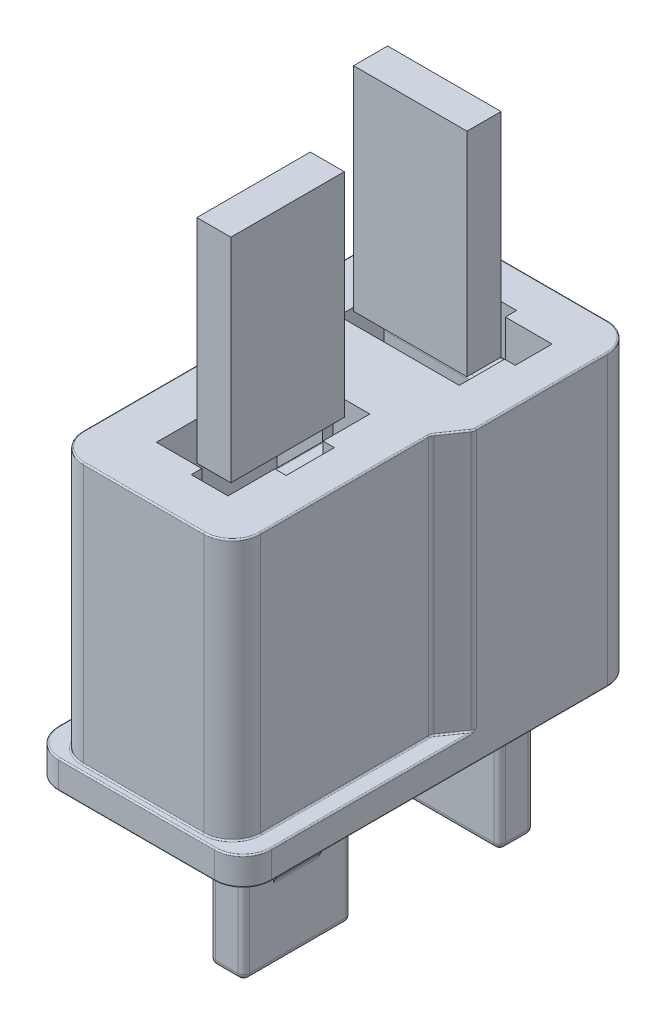
SolidWorks part; units mm, degrees
ref_plane "Front Plane" through (0, 0, 0) normal (0, 0, 1) x (1, 0, 0)
ref_plane "Top Plane" through (0, 0, 0) normal (0, 1, 0) x (1, 0, 0)
ref_plane "Right Plane" through (0, 0, 0) normal (1, 0, 0) x (0, 0, -1)
sketch "Sketch1" plane through (0, 0, 0) normal (0, 1, 0) x (1, 0, 0)
  line L1 (-3.75, -6.8) -> (3.75, -6.8)
  line L2 (-3.75, -6.8) -> (-3.75, 6.8)
  line L3 (-3.75, 6.8) -> (3.75, 6.8)
  line L4 (3.75, -6.8) -> (3.75, 6.8)
  line L5 (-3.75, -6.8) -> (3.75, 6.8) construction
  line L6 (-3.75, 6.8) -> (3.75, -6.8) construction
  point P0 (0, 0)
  dimension "D1" = 7.5
  dimension "D2" = 13.6
extrude "Boss-Extrude1" add sketch "Sketch1" along normal blind 7 and the other way blind 3.2
sketch "Sketch2" plane through (0, 7, 0) normal (0, 1, 0) x (1, 0, 0)
  line L0 (0, 0) -> (0, -6.8) construction
  line L1 (-3.75, -6.8) -> (3.75, -6.8) construction
  line L2 (3.125, -6.8) -> (3.125, 0.2)
  line L3 (3.125, 0.2) -> (3.75, 1.1)
  line L4 (3.75, -6.8) -> (3.75, 6.8) construction
  line L5 (3.75, 1.1) -> (3.75, -6.8)
  line L6 (3.75, -6.8) -> (3.125, -6.8)
  line L7 (-3.75, -6.8) -> (-3.125, -6.8)
  line L8 (-3.75, 1.1) -> (-3.75, -6.8)
  line L9 (-3.125, -6.8) -> (-3.125, 0.2)
  line L10 (-3.125, 0.2) -> (-3.75, 1.1)
  line L11 (3.75, 6.8) -> (-3.75, 6.8) construction
  dimension "D1" = 6.25
  dimension "D2" = 5.7
  dimension "D3" = 7
extrude "Cut-Extrude1" cut sketch "Sketch2" against normal through all
fillet "Fillet1" radius 1 4 edges at (-3.75, 1.9, -6.8) (3.75, 1.9, -6.8) (3.125, 1.9, 6.8) (-3.125, 1.9, 6.8)
fillet "Fillet2" radius 0.25 4 edges at (-3.125, 1.9, -0.2) (-3.75, 1.9, -1.1) (3.125, 1.9, -0.2) (3.75, 1.9, -1.1)
sketch "Sketch12" plane through (0, 7, 0) normal (0, 1, 0) x (1, 0, 0)
  line L0 (0, 0) -> (0, 4.45) construction
  line L1 (0, 0) -> (0, -2.75) construction
  line L2 (0, -2.75) -> (0.775, -2.75) construction
  line L3 (2.75, 6.8) -> (-2.75, 6.8) construction
  line L4 (-2.5, 5.1) -> (2.5, 5.1)
  line L5 (-2.5, 5.1) -> (-2.5, 3.8)
  line L6 (-2.5, 3.8) -> (2.5, 3.8)
  line L7 (2.5, 5.1) -> (2.5, 3.8)
  line L8 (-2.5, 5.1) -> (2.5, 3.8) construction
  line L9 (-2.5, 3.8) -> (2.5, 5.1) construction
  line L10 (0.125, -0.25) -> (1.425, -0.25)
  line L11 (0.125, -0.25) -> (0.125, -5.25)
  line L12 (0.125, -5.25) -> (1.425, -5.25)
  line L13 (1.425, -0.25) -> (1.425, -5.25)
  line L14 (0.125, -0.25) -> (1.425, -5.25) construction
  line L15 (0.125, -5.25) -> (1.425, -0.25) construction
  line L16 (3.125, 0.1217) -> (3.125, -5.8) construction
  line L17 (-2.125, -6.8) -> (2.125, -6.8) construction
  dimension "D1" = 5
  dimension "D2" = 1.3
  dimension "D3" = 1.7
  dimension "D4" = 1.7
  dimension "D5" = 1.55
extrude "Cut-Extrude4" cut sketch "Sketch12" against normal blind 8
sketch "Sketch13" plane through (0, 7, 0) normal (0, 1, 0) x (1, 0, 0)
  line L0 (0, 3.8) -> (0, 3) construction
  line L1 (-2.5, 3.8) -> (2.5, 3.8) construction
  line L2 (0.125, -2.75) -> (-0.675, -2.75) construction
  line L3 (0.125, -0.25) -> (0.125, -5.25) construction
  line L4 (-3.125, -5.8) -> (-3.125, 0.1217) construction
  line L5 (-2.125, 2.2) -> (2.125, 2.2)
  line L6 (-2.125, 2.2) -> (-2.125, 3.8)
  line L7 (-2.125, 3.8) -> (2.125, 3.8)
  line L8 (2.125, 2.2) -> (2.125, 3.8)
  line L9 (-2.125, 2.2) -> (2.125, 3.8) construction
  line L10 (-2.125, 3.8) -> (2.125, 2.2) construction
  line L11 (-1.475, -4.875) -> (0.125, -4.875)
  line L12 (-1.475, -4.875) -> (-1.475, -0.625)
  line L13 (-1.475, -0.625) -> (0.125, -0.625)
  line L14 (0.125, -4.875) -> (0.125, -0.625)
  line L15 (-1.475, -4.875) -> (0.125, -0.625) construction
  line L16 (-1.475, -0.625) -> (0.125, -4.875) construction
  dimension "D1" = 4.25
  dimension "D2" = 1.65
extrude "Cut-Extrude5" cut sketch "Sketch13" against normal up to surface (8 mm away) up to face at (0, -1, -4.45)
sketch "Sketch14" plane through (0, -3.2, 0) normal (0, -1, 0) x (1, 0, 0)
  line L0 (-3.75, -3.4891) -> (-3.75, 7.05)
  line L1 (-3.75, -5.8) -> (-3.75, -1.1783) construction
  line L2 (-3.75, 7.05) -> (3.75, 7.05)
  line L3 (3.75, 7.05) -> (3.75, -3.4891)
  line L4 (3.75, -1.1783) -> (3.75, -5.8) construction
  line L5 (3.75, -3.4891) -> (-3.75, -3.4891)
  line L6 (-2.125, 6.8) -> (2.125, 6.8) construction
  dimension "D1" = 0.25
extrude "Boss-Extrude5" add sketch "Sketch14" against normal blind 1
fillet "Fillet8" radius 1 2 edges at (3.75, -2.7, 7.05) (-3.75, -2.7, 7.05)
sketch "Sketch15" plane through (0, 7, 0) normal (0, 1, 0) x (1, 0, 0)
  line L0 (0, 5.1) -> (0, 5.3) construction
  line L1 (2.5, 5.1) -> (-2.5, 5.1) construction
  line L2 (1.425, -2.75) -> (1.625, -2.75) construction
  line L3 (1.425, -5.25) -> (1.425, -0.25) construction
  line L5 (-0.85, 5.5) -> (0.85, 5.5)
  line L6 (-0.85, 5.5) -> (-0.85, 5.1)
  line L7 (-0.85, 5.1) -> (0.85, 5.1)
  line L8 (0.85, 5.5) -> (0.85, 5.1)
  line L9 (-0.85, 5.5) -> (0.85, 5.1) construction
  line L10 (-0.85, 5.1) -> (0.85, 5.5) construction
  line L11 (1.825, -1.9) -> (1.425, -1.9)
  line L12 (1.825, -1.9) -> (1.825, -3.6)
  line L13 (1.825, -3.6) -> (1.425, -3.6)
  line L14 (1.425, -1.9) -> (1.425, -3.6)
  line L15 (1.825, -1.9) -> (1.425, -3.6) construction
  line L16 (1.825, -3.6) -> (1.425, -1.9) construction
  dimension "D1" = 1.7
  dimension "D2" = 0.4
extrude "Cut-Extrude6" cut sketch "Sketch15" against normal up to surface (8 mm away) up to face at (0, -1, -3.725)
sketch "Sketch16" plane through (0, -1, 0) normal (0, 1, 0) x (1, 0, 0)
  line L0 (-2.45, 5.05) -> (-2.45, 3.85)
  line L1 (-2.5, 5.1) -> (2.5, 5.1) construction
  line L2 (-2.5, 5.1) -> (-2.5, 3.8) construction
  line L3 (-2.5, 3.8) -> (2.5, 3.8) construction
  line L4 (2.5, 5.1) -> (2.5, 3.8) construction
  line L5 (-2.45, 3.85) -> (2.45, 3.85)
  line L6 (2.45, 5.05) -> (2.45, 3.85)
  line L7 (-2.45, 5.05) -> (2.45, 5.05)
  line L8 (1.375, -0.3) -> (1.375, -5.2)
  line L9 (1.425, -0.25) -> (0.125, -0.25) construction
  line L10 (1.425, -0.25) -> (1.425, -5.25) construction
  line L11 (1.425, -5.25) -> (0.125, -5.25) construction
  line L12 (0.125, -0.25) -> (0.125, -5.25) construction
  line L13 (1.375, -5.2) -> (0.175, -5.2)
  line L14 (0.175, -0.3) -> (0.175, -5.2)
  line L15 (1.375, -0.3) -> (0.175, -0.3)
  dimension "D1" = 0.05
  dimension "D2" = 0.05
extrude "Boss-Extrude6" add sketch "Sketch16" along normal blind 6.8
fillet "Fillet9" radius 0.1 16 edges at (1.375, 5.8, 2.75) (0.775, 5.8, 5.2) (0.175, 5.8, 2.75) (0.775, 5.8, 0.3) (2.45, 5.8, -4.45) (0, 5.8, -3.85) (-2.45, 5.8, -4.45) (0, 5.8, -5.05) (0.175, 2.4, 5.2) (1.375, 2.4, 5.2) (1.375, 2.4, 0.3) (0.175, 2.4, 0.3) (-2.45, 2.4, -5.05) (-2.45, 2.4, -3.85) (2.45, 2.4, -5.05) (2.45, 2.4, -3.85)
sketch "Sketch3" plane through (0, 7, 0) normal (0, 1, 0) x (1, 0, 0)
  line L0 (0, 0) -> (0, 3.2) construction
  line L1 (0, 0) -> (0, -2.8) construction
  line L2 (-2, 2.6) -> (2, 2.6)
  line L3 (-2, 2.6) -> (-2, 3.8)
  line L4 (-2, 3.8) -> (2, 3.8)
  line L5 (2, 2.6) -> (2, 3.8)
  line L6 (-2, 2.6) -> (2, 3.8) construction
  line L7 (-2, 3.8) -> (2, 2.6) construction
  line L8 (0, -2.8) -> (0.475, -2.8) construction
  line L9 (2.75, 6.8) -> (-2.75, 6.8) construction
  line L10 (-0.125, -4.8) -> (1.075, -4.8)
  line L11 (-0.125, -4.8) -> (-0.125, -0.8)
  line L12 (-0.125, -0.8) -> (1.075, -0.8)
  line L13 (1.075, -4.8) -> (1.075, -0.8)
  line L14 (-0.125, -4.8) -> (1.075, -0.8) construction
  line L15 (-0.125, -0.8) -> (1.075, -4.8) construction
  line L16 (-3.125, -5.8) -> (-3.125, 0.1217) construction
  line L17 (-2.125, -6.8) -> (2.125, -6.8) construction
  dimension "D1" = 4
  dimension "D2" = 1.2
  dimension "D3" = 3
  dimension "D4" = 3
  dimension "D5" = 2
extrude "Boss-Extrude2" add sketch "Sketch3" along normal blind 7.5
sketch "Sketch4" plane through (0, -3.2, 0) normal (0, -1, 0) x (1, 0, 0)
  line L0 (1.375, 2.75) -> (0.175, 2.75) construction
  line L2 (-2.35, -3.85) -> (2.35, -3.85) construction
  line L3 (0.175, 4.65) -> (1.375, 4.65)
  line L4 (0.175, 4.65) -> (0.175, 0.85)
  line L5 (0.175, 0.85) -> (1.375, 0.85)
  line L6 (1.375, 4.65) -> (1.375, 0.85)
  line L7 (0.175, 4.65) -> (1.375, 0.85) construction
  line L8 (0.175, 0.85) -> (1.375, 4.65) construction
  line L31 (2.35, -5.05) -> (-2.35, -5.05) construction
  line L32 (-2.35, -3.85) -> (2.35, -3.85) construction
  line L33 (2.35, -5.05) -> (-2.35, -5.05) construction
  line L34 (0.175, 0.4) -> (0.175, 5.1) construction
  line L35 (1.375, 5.1) -> (1.375, 0.4) construction
  line L36 (0.175, 0.4) -> (0.175, 5.1) construction
  line L37 (1.375, 5.1) -> (1.375, 0.4) construction
  line L38 (0, -5.05) -> (0, -3.85) construction
  line L40 (-1.9, -3.85) -> (1.9, -3.85)
  line L41 (-1.9, -3.85) -> (-1.9, -5.05)
  line L42 (-1.9, -5.05) -> (1.9, -5.05)
  line L43 (1.9, -3.85) -> (1.9, -5.05)
  line L44 (-1.9, -3.85) -> (1.9, -5.05) construction
  line L45 (-1.9, -5.05) -> (1.9, -3.85) construction
  point P2 (0.775, 2.75)
  point P32 (0, -4.45)
  dimension "D4" = 3.8
extrude "Boss-Extrude3" add sketch "Sketch4" along normal blind 5
sketch "Sketch5" plane through (0, 0, -3.85) normal (0, 0, 1) x (1, 0, 0)
  line L0 (0, -3.2) -> (0, -5.2) construction
  line L2 (0.8, -3.2) -> (-0.8, -3.2)
  line L3 (-0.8, -3.2) -> (-0.8, -5.2)
  line L4 (-0.8, -5.2) -> (0.8, -5.2)
  line L5 (0.8, -3.2) -> (0.8, -5.2)
  line L6 (1.9, -3.2) -> (-1.9, -3.2) construction
  dimension "D1" = 1.6
  dimension "D2" = 2
extrude "Cut-Extrude2" cut sketch "Sketch5" against normal up to next (1.2 mm away)
sketch "Sketch6" plane through (-0.8, 0, 0) normal (1, 0, 0) x (0, 0, -1)
  line L0 (4.35, -3.2) -> (4.35, -4)
  line L1 (5.05, -3.2) -> (3.85, -3.2) construction
  line L3 (3.85, -3.2) -> (3.85, -5.2) construction
  arc A0 (4.35, -4) -> (3.85, -5.2) centre (2.66, -4) cw
  dimension "D1" = 0.5
  dimension "D2" = 0.8
extrude "Extrude-Thin1" add sketch "Sketch6" along normal up to surface (1.6 mm away) thin up to face at (0.8, -4.2, -4.45) thin type one direction reverse wall 1.2
sketch "Sketch7" plane through (1.375, 0, 0) normal (1, 0, 0) x (0, 0, -1)
  line L0 (3.85, -3.2) -> (3.85, -5.2) construction
  line L1 (-2.8, -3.2) -> (-2.8, -5.2) construction
  line L2 (-2, -5.2) -> (-3.6, -5.2)
  line L3 (-3.6, -5.2) -> (-3.6, -3.2)
  line L4 (-3.6, -3.2) -> (-2, -3.2)
  line L5 (-2, -5.2) -> (-2, -3.2)
  line L7 (-0.85, -3.2) -> (-4.65, -3.2) construction
  dimension "D1" = 1.6
extrude "Cut-Extrude3" cut sketch "Sketch7" against normal through all
sketch "Sketch8" plane through (0, 0, 3.6) normal (0, 0, -1) x (-1, 0, 0)
  line L0 (-0.675, -3.2) -> (-0.675, -4)
  line L1 (-0.175, -3.2) -> (-1.375, -3.2) construction
  line L2 (0.8, -3.2) -> (0.8, -4) construction
  line L3 (-0.175, -3.2) -> (-0.175, -5.2) construction
  line L4 (-0.675, -3.2) -> (-1.075, -3.2) construction
  arc A0 (-0.675, -4) -> (-0.175, -5.2) centre (1.015, -4) ccw
  dimension "D1" = 0.5
extrude "Extrude-Thin2" add sketch "Sketch8" along normal up to surface (1.6 mm away) thin up to face at (0.775, -4.2, 2) thin type one direction wall 1.2
sketch "Sketch9" plane through (0, -3.2, 0) normal (0, -1, 0) x (1, 0, 0)
  line L0 (-1.125, 2.8) -> (0.675, 2.8) construction
  line L1 (0.675, 2) -> (0.675, 3.6) construction
  line L2 (-1.125, 3.8) -> (-1.125, 1.8) construction
  line L3 (-0.975, 3.8) -> (-0.975, 1.8)
  line L4 (-1.275, 3.8) -> (-1.275, 1.8)
  line L5 (0.175, 4.65) -> (0.175, 3.6) construction
  line L6 (0, -4.35) -> (0, -2.35) construction
  line L7 (0.8, -4.35) -> (-0.8, -4.35) construction
  line L8 (1, -2.35) -> (-1, -2.35) construction
  line L10 (1, -2.5) -> (-1, -2.5)
  line L11 (1, -2.2) -> (-1, -2.2)
  line L12 (0, -3.35) -> (0, -1.35) construction
  line L13 (-0.15, -3.35) -> (-0.15, -1.35)
  line L14 (0.15, -3.35) -> (0.15, -1.35)
  line L15 (-0.8, -3.85) -> (-1.9, -3.85) construction
  arc A0 (-0.975, 3.8) -> (-1.275, 3.8) centre (-1.125, 3.8) ccw
  arc A1 (-1.275, 1.8) -> (-0.975, 1.8) centre (-1.125, 1.8) ccw
  arc A2 (1, -2.5) -> (1, -2.2) centre (1, -2.35) ccw
  arc A3 (-1, -2.2) -> (-1, -2.5) centre (-1, -2.35) ccw
  arc A4 (-0.15, -3.35) -> (0.15, -3.35) centre (0, -3.35) ccw
  arc A5 (0.15, -1.35) -> (-0.15, -1.35) centre (0, -1.35) ccw
  point P6 (-1.125, 2.8)
  point P20 (0, -2.35)
  point P29 (0, -2.35)
  dimension "D4" = 0.15
  dimension "D3" = 1.5
  dimension "D1" = 1.3
  dimension "D2" = 2
extrude "Boss-Extrude4" add sketch "Sketch9" along normal blind 0.11 contours L4 A1 L3 A0 | L14 A5 L13 L11 | L10 A2 L11 L14 | L13 A4 L14 L10 | L11 A3 L10 L13 | L10 L14 L11 L13
fillet "Fillet3" radius 0.1 16 edges at (-1.125, -3.31, 3.95) (-0.975, -3.31, 2.8) (-1.125, -3.31, 1.65) (-1.275, -3.31, 2.8) (0.575, -3.31, -2.2) (1.15, -3.31, -2.35) (0.575, -3.31, -2.5) (0.15, -3.31, -2.925) (0, -3.31, -3.5) (-0.15, -3.31, -2.925) (-0.575, -3.31, -2.5) (-1.15, -3.31, -2.35) (-0.575, -3.31, -2.2) (-0.15, -3.31, -1.775) (0, -3.31, -1.2) (0.15, -3.31, -1.775)
fillet "Fillet4" radius 0.2 20 edges at (0, -8.2, -5.05) (-1.9, -8.2, -4.45) (0, -8.2, -3.85) (1.9, -8.2, -4.45) (0.775, -8.2, 0.85) (0.175, -8.2, 2.75) (0.775, -8.2, 4.65) (1.375, -8.2, 2.75) (0, -5.6248, -5.05) (1.375, -5.6248, 2.8) (0.175, -5.2, 2.8) (1.375, -5.7, 4.65) (1.375, -5.7, 0.85) (0.175, -5.7, 0.85) (0.175, -5.7, 4.65) (0, -5.2, -3.85) (1.9, -5.7, -3.85) (1.9, -5.7, -5.05) (-1.9, -5.7, -5.05) (-1.9, -5.7, -3.85)
fillet "Fillet5" [suppressed] radius 0.05
fillet "Fillet6" radius 0.05 40 edges at (-3.4571, 7, -6.5071) (0, 7, -6.8) (3.4571, 7, -6.5071) (3.75, 7, -3.4891) (3.7386, 7, -1.1036) (3.4375, 7, -0.65) (3.1364, 7, -0.1964) (3.125, 7, 2.8391) (2.8321, 7, 6.5071) (0, 7, 6.8) (-2.8321, 7, 6.5071) (-3.125, 7, 2.8391) (-3.1364, 7, -0.1964) (-3.4375, 7, -0.65) (-3.7386, 7, -1.1036) (-3.4571, -3.2, -6.5071) (0, -3.2, -6.8) (3.4571, -3.2, -6.5071) (3.75, -3.2, 0.125) (-3.75, 7, -3.4891) (-3.75, -3.2, 0.125) (3.4571, -3.2, 6.7571) (0, -3.2, 7.05) (-3.4571, -3.2, 6.7571) (-3.4571, -2.2, 6.7571) (-3.75, -2.2, 2.4359) (-3.7386, -2.2, -1.1036) (-3.4375, -2.2, -0.65) (-3.1364, -2.2, -0.1964) (-3.125, -2.2, 2.8391) (-2.8321, -2.2, 6.5071) (0, -2.2, 6.8) (2.8321, -2.2, 6.5071) (3.125, -2.2, 2.8391) (3.1364, -2.2, -0.1964) (3.4375, -2.2, -0.65) (3.7386, -2.2, -1.1036) (3.75, -2.2, 2.4359) (3.4571, -2.2, 6.7571) (0, -2.2, 7.05)
